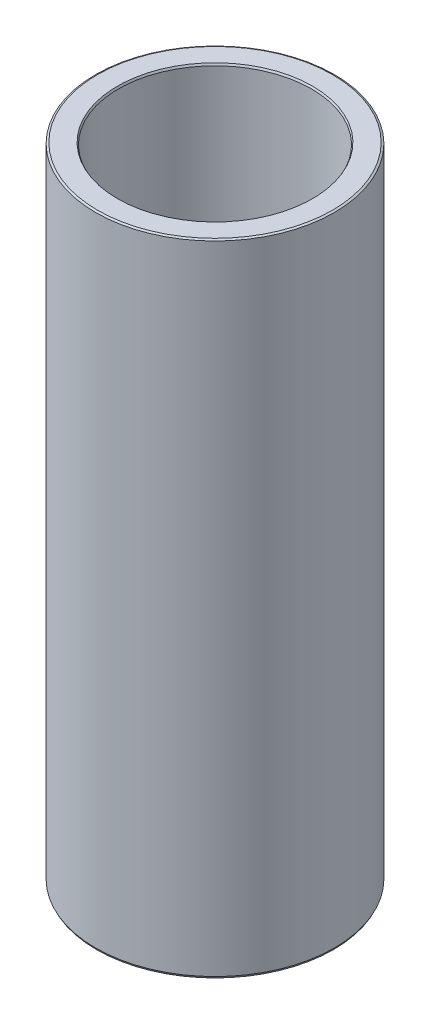
SolidWorks part; units mm, degrees
ref_plane "Front Plane" through (0, 0, 0) normal (0, 0, 1) x (1, 0, 0)
ref_plane "Top Plane" through (0, 0, 0) normal (0, 1, 0) x (1, 0, 0)
ref_plane "Right Plane" through (0, 0, 0) normal (1, 0, 0) x (0, 0, -1)
sketch "Sketch1" plane through (0, 0, 0) normal (0, 1, 0) x (1, 0, 0)
  circle A0 centre (0, 0) radius 30
  dimension "SLEEVE_OD" = 60
extrude "Boss-Extrude1" add sketch "Sketch1" along normal blind 160.7376
sketch "Sketch2" plane through (0, 0, 0) normal (0, 1, 0) x (1, 0, 0)
  circle A0 centre (0, 0) radius 24.2557
  dimension "BORE_D" = 48.5113
extrude "Cut-Extrude1" cut sketch "Sketch2" along normal through all
chamfer "Chamfer1" distance 0.2449 angle 63.161 4 edges at (0, 160.7376, 24.2557) (0, 0, 24.2557) (0, 0, 30) (0, 160.7376, 30) first distance on face at (0, 160.7376, 24.2557) first distance on face at (0, 0, 24.2557) first distance on face at (0, 160.7376, 30)
